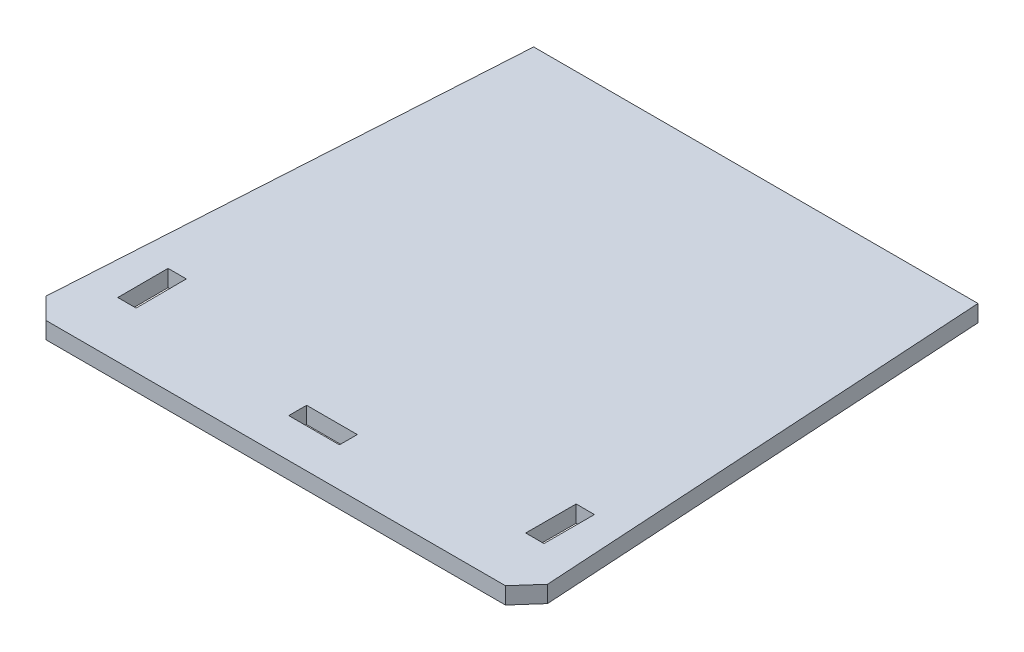
SolidWorks part; units mm, degrees
note: '?' marks a value the reader was unsure of.
ref_plane "Front Plane" through (0, 0, 0) normal (0, 0, 1) x (1, 0, 0)
ref_plane "Top Plane" through (0, 0, 0) normal (0, 1, 0) x (1, 0, 0)
ref_plane "Right Plane" through (0, 0, 0) normal (1, 0, 0) x (0, 0, -1)
ref_axis "Axis8" through (88.99, 0, -5.0102) along (-1, 0, 0)?
sketch "Sketch1" plane through (0, 0, 0) normal (0, 1, 0) x (1, 0, 0)
  line L0 (-225, 0) -> (225, 0) construction
  line L1 (-225, 0) -> (225, 0) construction
  line L2 (-225, 0) -> (-225, -410.1219) construction
  line L3 (-225, -410.1219) -> (225, -410.1219) construction
  line L4 (225, 0) -> (225, -410.1219) construction
  line L6 (0, 0) -> (0, -410.1219) construction
  line L7 (-200, 5.0102) -> (199.6946, 5.0102) construction
  line L8 (-225, -410.1219) -> (-198.7802, 20.0102)
  line L9 (88.99, 5.0102) -> (-88.99, 5.0102) construction
  line L10 (198.7802, 20.0102) -> (225, -410.1219)
  line L12 (225, -410.1219) -> (-225, -410.1219)
  line L13 (-198.7802, 20.0102) -> (198.7802, 20.0102)
  line L20 (-200, 0) -> (-225, 0) construction
  dimension "D1" = 15
  dimension "D3" = 25
extrude "Boss-Extrude1" add sketch "Sketch1" against normal blind 15
ref_axis "Axis1" through (191.4735, -15, -20.0102) along (-0.0021, 0, 1)?
ref_axis "Axis2" through (174.9542, 0, 50.3733) along (0.0021, 0, -1)?
sketch "Sketch2" plane through (0, -15, 0) normal (0, -1, 0) x (1, 0, 0)
  line L0 (190.6624, 360.2449) -> (190.7585, 315.1669)
  line L1 (190.7585, 315.1669) -> (174.3894, 315.132)
  line L2 (174.3894, 315.132) -> (174.2932, 360.21)
  line L3 (174.2932, 360.21) -> (190.6624, 360.2449)
  line L4 (191.4735, -20.0102) -> (190.556, 410.1219) construction
  line L5 (174.9542, 50.3733) -> (175.4875, -199.6261) construction
  line L8 (175.7194, 360.2131) -> (175.8156, 315.135) construction
  line L9 (190.7585, 315.1669) -> (191.4735, -20.0102) construction
extrude "Cut-Extrude1" cut sketch "Sketch2" against normal through all
mirror "Mirror1" about plane through (0, 0, 0) normal (1, 0, 0) of "Cut-Extrude1"
chamfer "Chamfer1" distance 20 angle 45 2 edges at (225, -7.5, 410.1219) (-225, -7.5, 410.1219)
ref_axis "Axis3" through (-175.1675, 0, -49.6264) along (0.0021, 0, 1)?
ref_axis "Axis4" through (174.9542, 0, 50.3733) along (0.0021, 0, -1)?
ref_axis "Axis5" through (204.6553, 0, 359.2654) along (1, 0, 0)?
ref_axis "Axis6" through (-222.8161, 0, 374.2954) along (1, 0, 0)?
ref_axis "Axis7" through (221.8999, 0, 359.2654) along (-1, 0, 0)?
sketch "Sketch4" plane through (0, 0, 0) normal (0, 1, 0) x (1, 0, 0)
  line L0 (-22.6879, -359.2654) -> (-22.6879, -375.2449)
  line L1 (-22.6879, -375.2449) -> (22.6879, -375.2449)
  line L2 (22.6879, -375.2449) -> (22.6879, -359.2654)
  line L3 (22.6879, -359.2654) -> (-22.6879, -359.2654)
  line L6 (221.8999, -359.2654) -> (-221.8999, -359.2654) construction
  line L7 (0, -359.2654) -> (0, -375.2449) construction
  line L10 (0, -8.25) -> (0, 8.25) construction
  line L11 (-22.6879, -374.2954) -> (22.6879, -374.2954) construction
  line L12 (-222.8161, -374.2954) -> (222.8161, -374.2954) construction
extrude "Cut-Extrude5" cut sketch "Sketch4" against normal through all
